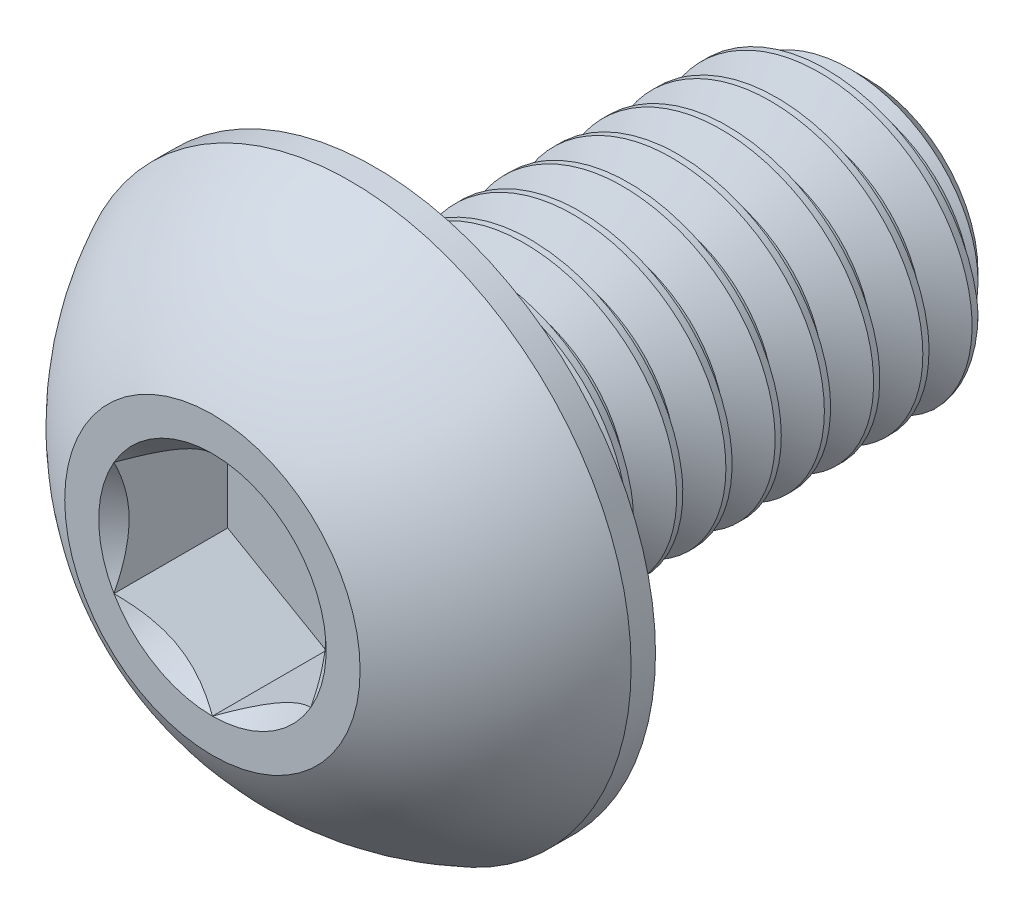
SolidWorks part; units mm, degrees
ref_plane "Front" through (0, 0, 0) normal (0, 0, 1) x (1, 0, 0)
ref_plane "Top" through (0, 0, 0) normal (0, 1, 0) x (1, 0, 0)
ref_plane "Right" through (0, 0, 0) normal (1, 0, 0) x (0, 0, -1)
sketch "Sketch1" plane through (0, 0, 0) normal (1, 0, 0) x (0, 0, -1)
  line L2 (1.65, 1.5) -> (6.65, 1.5)
  line L3 (6.65, 1.5) -> (6.65, 0)
  line L4 (6.65, 0) -> (1.65, 0)
  line L6 (1.4025, 2.85) -> (1.65, 2.85) construction
  line L7 (6.65, 1.5) -> (6.65, -1.5) construction
  line L8 (0, 0) -> (1.65, 0) construction
  line L9 (1.65, 2.85) -> (1.65, -2.85) construction
  line L11 (1.65, 1.5) -> (1.65, 0)
  line L13 (0, 1) -> (0, -1) construction
  line L14 (0, 1) -> (0, 1.5) construction
  arc A3 (0, 1.5) -> (1.4025, 2.85) centre (2.7948, 0) cw construction
  dimension "D1" = 0.2475
revolve "Revolve1" add sketch "Sketch1" angle 360 mid plane about L4
sketch "Sketch3" plane through (0, 0, -6.65) normal (0, 0, -1) x (-1, 0, 0)
  circle A0 centre (0, 0) radius 1.5
curve "Helix/Spiral1" pitch 0.5 height 5.5 radius 1.5 centre (0, 0, -6.65) axis (0, 0, 1) start towards (0, 1, 0)
sketch "Sketch2" plane through (0, 0, 0) normal (1, 0, 0) x (0, 0, -1)
  line L0 (6.65, 1.5) -> (7.0875, 1.5)
  line L1 (7.0875, 1.5) -> (6.9, 1.1752)
  line L2 (6.9, 1.1752) -> (6.8375, 1.1752)
  line L3 (6.8375, 1.1752) -> (6.65, 1.5)
  line L4 (6.7438, 1.3376) -> (6.9938, 1.3376) construction
  dimension "D1" = 60
  dimension "D2" = 0.0625
  dimension "D3" = 0.25
chamfer "Chamfer1" distance 0.375 angle 45 1 edges at (0, 1.5, -6.65)
sweep "Cut-Sweep1" cut profiles "Sketch2" path "Helix/Spiral1" align with end faces yes
sketch "Sketch7" plane through (0, 0, 0) normal (1, 0, 0) x (0, 0, -1)
  line L6 (1.4025, 2.85) -> (1.65, 2.85) construction
  line L8 (0, 0) -> (1.65, 0) construction
  line L11 (1.65, 2.85) -> (1.65, -2.85) construction
  line L12 (1.4025, 2.85) -> (1.65, 2.85)
  line L13 (0, 0) -> (1.65, 0)
  line L14 (0, 1) -> (0, -1) construction
  line L15 (1.65, 2.85) -> (1.65, 0)
  line L16 (0, 1.5) -> (0, 0)
  arc A2 (1.4025, 2.85) -> (0, 1.5) centre (2.7948, 0) ccw construction
  arc A3 (1.4025, 2.85) -> (0, 1.5) centre (2.7948, 0) ccw
revolve "Revolve2" add sketch "Sketch7" angle 360 mid plane about L13
sketch "Sketch5" plane through (0, 0, 0) normal (0, 0, 1) x (1, 0, 0)
  line L1 (1, -0.5774) -> (1, 0.5774)
  line L2 (1, 0.5774) -> (0, 1.1547)
  line L3 (0, 1.1547) -> (-1, 0.5774)
  line L4 (-1, 0.5774) -> (-1, -0.5774)
  line L5 (-1, -0.5774) -> (0, -1.1547)
  line L6 (0, -1.1547) -> (1, -0.5774)
  circle A0 centre (0, 0) radius 1 construction
extrude "Cut-Extrude2" cut sketch "Sketch5" against normal blind 1.155
sketch "Sketch6" plane through (0, 0, 0) normal (0, 0, 1) x (1, 0, 0)
  circle A0 centre (0, 0) radius 1.1547
extrude "Cut-Extrude3" cut sketch "Sketch6" against normal blind 1.155 draft 45
sketch "Sketch9" [suppressed] plane through (0, 0, -4.2164) normal (0, 0, 1) x (1, 0, 0)
  circle A2 centre (0, 0) radius 3.9687
extrude "Boss-Extrude2" [suppressed] add sketch "Sketch9" against normal offset from surface (9.525 mm away) 28.575 up to face at (0, 1.125, -6.65)
sketch "Sketch10" plane through (0, 0, 0) normal (1, 0, 0) x (0, 0, -1)
  line L0 (6.65, 1.5) -> (6.65, -1.5) construction
  point P0 (5.9, -1.5)
  dimension "D1" = 0.75
equation "\"D3@Helix/Spiral1\" = \"Lg@Sketch1\" + \"D4@Helix/Spiral1\""
equation "\"D2@Sketch2\" = \"D4@Helix/Spiral1\" * .125"
equation "\"D3@Sketch2\" = \"D4@Helix/Spiral1\" * .5"
equation "\"D1@Chamfer1\" = \"D4@Helix/Spiral1\" * .75"
equation "\"D1@Cut-Extrude2\" = \"Head Ht@Sketch1\" * .7"
equation "\"D1@Sketch1\" = \"Head Ht@Sketch1\" * .15"
equation "\"D1@Sketch10\" = \"D4@Helix/Spiral1\" * 1.5"
equation "\"D1@Cut-Extrude3\" = \"D1@Cut-Extrude2\""
